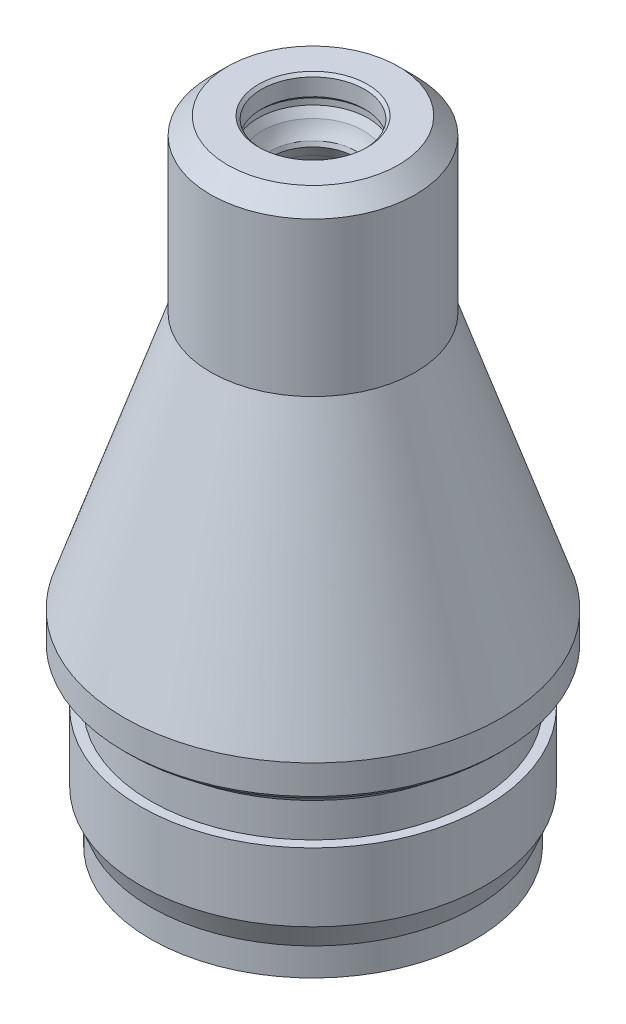
SolidWorks part; units mm, degrees
ref_plane "정면" through (0, 0, 0) normal (0, 0, 1) x (1, 0, 0)
ref_plane "윗면" through (0, 0, 0) normal (0, 1, 0) x (1, 0, 0)
ref_plane "우측면" through (0, 0, 0) normal (1, 0, 0) x (0, 0, -1)
sketch "스케치1" plane through (0, 0, 0) normal (1, 0, 0) x (0, 0, -1)
  line L0 (0, 0) -> (4.2, 0) construction
  line L1 (4.2, 0) -> (4.2, 1)
  line L2 (3.1896, 35) -> (6, 35)
  line L3 (6, 35) -> (6, 25)
  line L4 (6, 25) -> (11.05, 10)
  line L5 (11.05, 10) -> (11.05, 8)
  line L6 (9.6567, 0) -> (4.2, 0) construction
  line L7 (10.05, 8) -> (9.5, 7)
  line L8 (9.5, 7) -> (9.5, 5)
  line L9 (0, 0) -> (0, 33.7416) construction
  line L10 (11.05, 8) -> (10.05, 8)
  line L11 (9.5, 5) -> (10.075, 5)
  line L12 (9.5, -2) -> (9.5, -0.3746)
  line L13 (3.1896, 35) -> (3.02, 34.8304)
  line L14 (3.02, 34.8304) -> (3.02, 33.8304)
  line L15 (2.3992, 31.7786) -> (2.8027, 31)
  line L16 (3.02, 33.8304) -> (3.23, 33.6204)
  line L17 (10.075, 1) -> (9.5, -0.3746)
  line L19 (2.8027, 31) -> (4.2, 31) construction
  line L30 (9.5, -2) -> (4.2, -2)
  line L31 (4.2, -2) -> (4.2, 0)
  line L38 (10.075, 5) -> (10.075, 1)
  line L39 (3.23, 33.6204) -> (3.23, 33.2604)
  line L40 (4.2, 31) -> (4.2, 28) construction
  line L41 (4.2, 28) -> (3.5337, 29.4305)
  line L42 (3.5337, 29.4305) -> (2.8027, 31)
  line L43 (3.23, 33.2604) -> (2.9466, 32.7786)
  line L49 (4.2, 8.5) -> (4.7, 8)
  line L50 (4.7, 8) -> (4.7, 7.5)
  line L51 (4.7, 7.5) -> (4.2, 7)
  line L52 (4.2, 11.5) -> (4.7, 11)
  line L53 (4.7, 11) -> (4.7, 10.5)
  line L54 (4.7, 10.5) -> (4.2, 10)
  line L55 (4.2, 14.5) -> (4.7, 14)
  line L56 (4.7, 14) -> (4.7, 13.5)
  line L57 (4.7, 13.5) -> (4.2, 13)
  line L58 (4.2, 14.5) -> (4.2, 28)
  line L59 (4.2, 11.5) -> (4.2, 13)
  line L60 (4.2, 8.5) -> (4.2, 10)
  line L61 (4.2, 1) -> (4.2, 7)
  circle A1 centre (0, 33.7416) radius 3 construction
  arc A2 (2.3992, 31.7786) -> (2.9466, 32.7786) centre (0, 33.7416) ccw
  dimension "D10" = 3
  dimension "D13" = 6
  dimension "D14" = 31
  dimension "D17" = 3.1
  dimension "D1" = 10
  dimension "D2" = 2
  dimension "D3" = 20.15
  dimension "D4" = 15
  dimension "D5" = 19
  dimension "D6" = 4.2
  dimension "D7" = 1
  dimension "D8" = 6
  dimension "D9" = 10
  dimension "D11" = 3
  dimension "D12" = 1
  dimension "D15" = 3.02
  dimension "D16" = 135
  dimension "D18" = 135
  dimension "D19" = 2
  dimension "D20" = 2
  dimension "D21" = 1
  dimension "D28" = 28
revolve "회전1" add sketch "스케치1" angle 360 about L9
chamfer "모따기1" distance 1 angle 45 2 edges at (0, 35, -6) (0, -2, -4.2)
chamfer "모따기2" distance 0.1 angle 45 1 edges at (0, 31.7786, -2.3992) first distance on face at (0, 31, -2.8027)
ref_plane "평면1" through (-11.05, 0, 0) normal (-1, 0, 0) x (0, 0, 1)
sketch "스케치2" plane through (-11.05, 0, 0) normal (-1, 0, 0) x (0, 0, 1)
  line L0 (6, 3) -> (6, 0) construction
  line L2 (6, 0) -> (0, 0) construction
  circle A0 centre (6, 3) radius 1.25
  dimension "D1" = 2.5
  dimension "D2" = 3
  dimension "D3" = 6
extrude "컷-돌출1" [suppressed] cut sketch "스케치2" against normal blind 30
mirror "대칭 복사1" [suppressed] about plane through (0, 0, 0) normal (0, 0, 1)
chamfer "모따기3" distance 0.3 angle 45 1 edges at (0, 8, -11.05)
sketch "스케치3" [suppressed] plane through (0, 0, 0) normal (0, 1, 0) x (1, 0, 0)
  line L0 (0, -4.75) -> (0, -7.25) construction
  line L1 (8.885, -4.75) -> (-8.885, -4.75) construction
  line L2 (-6.9959, -7.25) -> (6.9959, -7.25) construction
  line L3 (9.2195, -6) -> (-9.2195, -6)
  circle A0 centre (0, 0) radius 11
  point P12 (0, -6)
  dimension "D1" = 22
